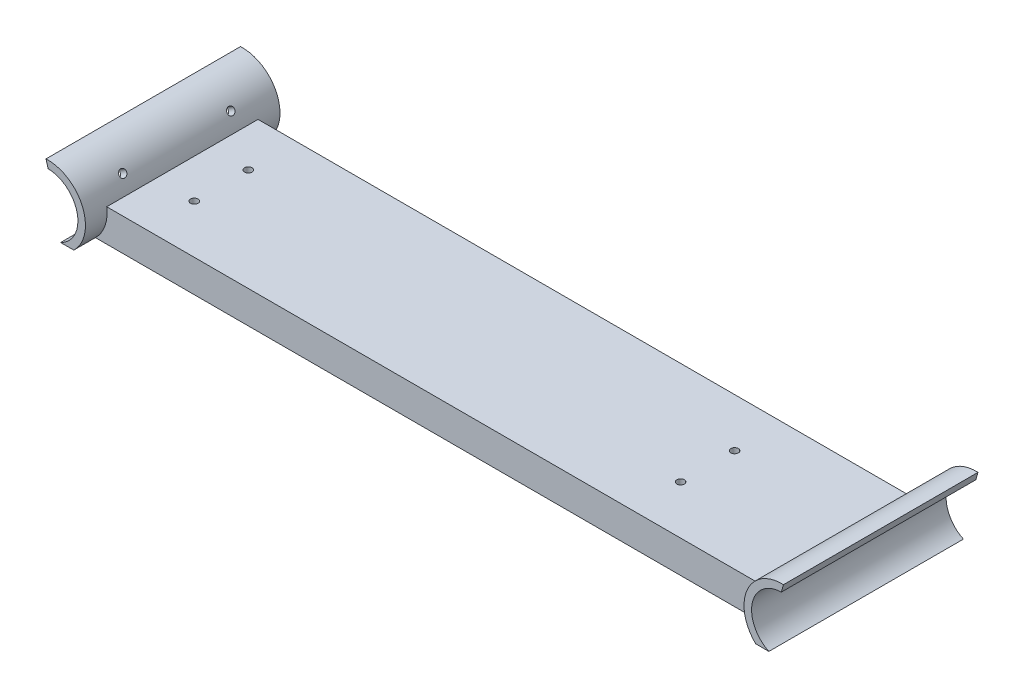
SolidWorks part; units mm, degrees
note: The reader was unsure of these and kept them because the rebuilt part matched: shared geometry of "Sketch2<3>".
material "1060 Alloy"
ref_plane "Plano frontal" through (0, 0, 0) normal (0, 0, 1) x (1, 0, 0)
ref_plane "Plano superior" through (0, 0, 0) normal (0, 1, 0) x (1, 0, 0)
ref_plane "Plano direito" through (0, 0, 0) normal (1, 0, 0) x (0, 0, -1)
sketch "Sketch2" plane through (0, 0, 0) normal (0, 0, 1) x (1, 0, 0)
  line L0 (-71.499, 0) -> (559.499, 0)
  line L2 (549, 30) -> (-61, 30)
  line L6 (585.1959, 60.2681) -> (583.1968, 53.2966)
  line L7 (571.6885, 0) -> (559.499, 0)
  line L8 (244, 60) -> (244, 0)
  line L9 (-83.6885, 0) -> (-71.499, 0)
  line L10 (-97.1959, 60.2681) -> (-95.1968, 53.2966)
  arc A2 (585.1959, 60.2681) -> (559.499, 0) centre (583.6831, 25.3008) ccw
  arc A3 (583.1968, 53.2966) -> (571.6885, 0) centre (583.6831, 25.3008) ccw
  arc A4 (-97.1959, 60.2681) -> (-71.499, 0) centre (-95.6831, 25.3008) cw
  arc A5 (-95.1968, 53.2966) -> (-83.6885, 0) centre (-95.6831, 25.3008) cw
  point P4 (0, 30)
  point P6 (400, 30)
  point P14 (244, 30)
  dimension "D5" = 35
  dimension "D6" = 28
  dimension "D2" = 24.1841
  dimension "D3" = 61
  dimension "D4" = 400
  dimension "D7" = 610
  dimension "D8" = 106
  dimension "D9" = 34.1968
  dimension "D10" = 30
extrude "Boss-Extrude3" add sketch "Sketch2" along normal mid plane 140 contours L2 A4 L0 L8 | A2 L2 L8 L0
extrude "Boss-Extrude4" add sketch "Sketch2<3>" along normal mid plane 180 contours L9 A5 L10 A4 | L7 A3 L6 A2
sketch "Sketch2<3>" plane through (0, 0, 0) normal (0, 0, 1) x (1, 0, 0) same geometry as "Sketch2"
hole_wizard "M8 Tapped Hole2" positions "3DSketch1" profile "Sketch9" tap size "M8" standard "ISO" end condition up to next
sketch3d "3DSketch1"
  line L0 (571.6885, 0, 90) -> (571.6885, 0, -90) construction
  point P0 (560.0801, 40.3639, 50)
  dimension "D1" = 50
  dimension "D2" = 42
sketch "Sketch9" plane through (560.0801, 40.3639, 50) normal (0, 0, 1) x (0.538, 0.843, 0)
  line L0 (0, 0) -> (0, 7)
  line L1 (0, 7) -> (3.4, 7)
  line L2 (3.4, 7) -> (3.4, 0)
  line L5 (3.4, 0) -> (0, 0)
  line L11 (0, -6.35) -> (0, 107.95) construction
  dimension "Thread Major Dia." = 6.8
  dimension "Thru Tap Drill Depth" = 7
mirror "Mirror4" about plane through (0, 0, 0) normal (0, 0, 1) of "M8 Tapped Hole2"
sketch "Sketch10" plane through (0, 0, 70) normal (0, 0, 1) x (1, 0, 0)
  line L0 (244, -127.5) -> (244, 187.5) construction
  line L1 (549, 30) -> (-61, 30) construction
  point P3 (244, 30)
  point P6 (244, 30)
  dimension "D1" = 315
  dimension "D2" = 157.5
ref_plane "PlanoMedio" through (244, 0, 0) normal (-1, 0, 0) x (0, 1, 0)
mirror "Mirror5" about plane through (244, 0, 0) normal (-1, 0, 0) of "Mirror4", "M8 Tapped Hole2"
sketch "Sketch11" plane through (0, 30, 0) normal (0, 1, 0) x (1, 0, 0)
  line L0 (0, 0) -> (0, 70)
  line L1 (549, 70) -> (-61, 70) construction
  line L2 (0, 70) -> (0, -70) construction
  line L3 (549, -70) -> (-61, -70) construction
hole_wizard "M8x1.0 Tapped Hole1" positions "Sketch13" profile "Sketch14" tap size "M8x1.0" standard "ISO"
sketch "Sketch13" plane through (0, 30, 0) normal (0, 1, 0) x (1, 0, 0)
  line L0 (0, -119.6217) -> (0, 119.6217) construction
  line L1 (549, 70) -> (-61, 70) construction
  point P0 (425, 25)
  point P2 (425, -25)
  dimension "D1" = 425
  dimension "D2" = 50
  dimension "D3" = 45
sketch "Sketch14" plane through (425, 30, -25) normal (1, 0, 0) x (0, 0, 1)
  line L0 (0, 0) -> (0, 13.103)
  line L1 (0, 13.103) -> (3.5, 11)
  line L2 (3.5, 11) -> (3.5, 0)
  line L5 (3.5, 0) -> (0, 0)
  line L10 (0, 13.103) -> (-3.5, 11) construction
  line L11 (0, -6.35) -> (0, 107.95) construction
  dimension "Tap Drill Dia." = 7
  dimension "Tap Drill Depth" = 11
  dimension "Drill Angle" = 118
cosmetic thread "Hole Thread1" parameters "D1"=5, "D2"=8
cosmetic thread "Hole Thread2" parameters "D1"=5, "D2"=8
hole_wizard "M8x1.0 Tapped Hole2" positions "Sketch15" profile "Sketch16" tap size "M8x1.0" standard "ISO"
sketch "Sketch15" plane through (0, 30, 0) normal (0, 1, 0) x (1, 0, 0)
  line L0 (0, -119.6217) -> (0, 119.6217) construction
  line L1 (549, 70) -> (-61, 70) construction
  point P0 (-25, 25)
  point P2 (-25, -25)
  dimension "D1" = 25
  dimension "D2" = 50
  dimension "D3" = 45
sketch "Sketch16" plane through (-25, 30, -25) normal (1, 0, 0) x (0, 0, 1)
  line L0 (0, 0) -> (0, 13.103)
  line L1 (0, 13.103) -> (3.5, 11)
  line L2 (3.5, 11) -> (3.5, 0)
  line L5 (3.5, 0) -> (0, 0)
  line L10 (0, 13.103) -> (-3.5, 11) construction
  line L11 (0, -6.35) -> (0, 107.95) construction
  dimension "Tap Drill Dia." = 7
  dimension "Tap Drill Depth" = 11
  dimension "Drill Angle" = 118
cosmetic thread "Hole Thread3" parameters "D1"=5, "D2"=8
cosmetic thread "Hole Thread4" parameters "D1"=5, "D2"=8
